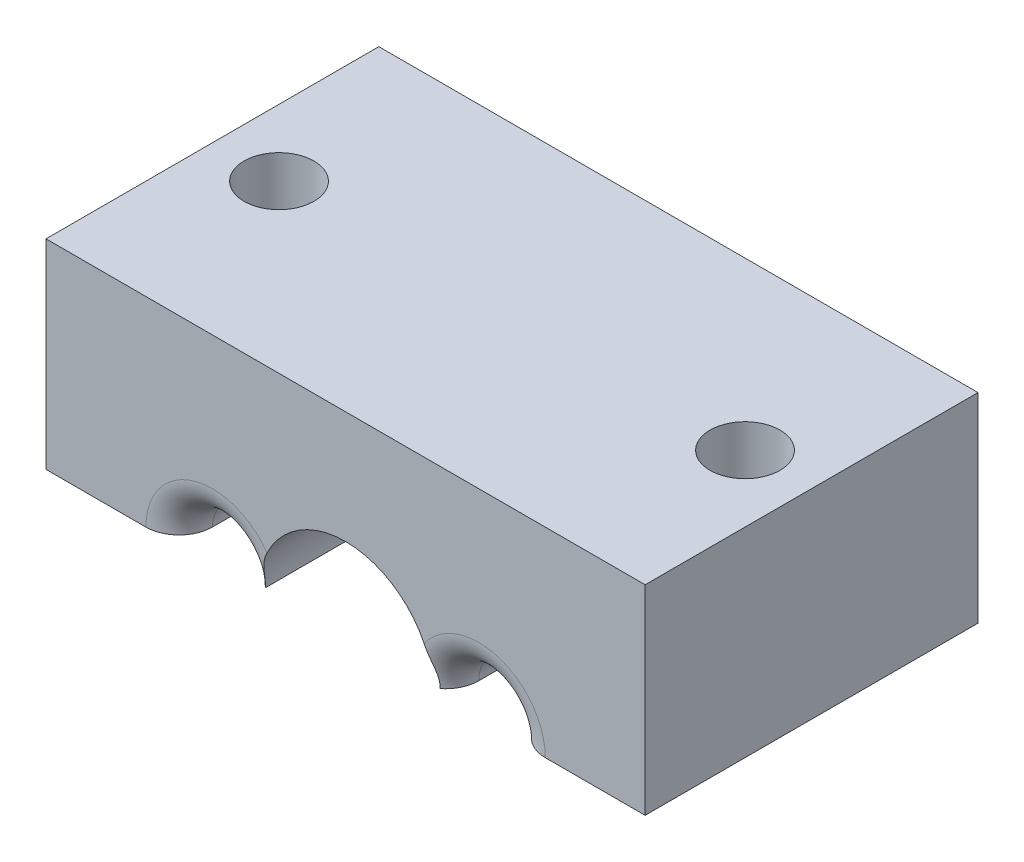
SolidWorks part; units mm, degrees
ref_plane "Front Plane" through (0, 0, 0) normal (0, 0, 1) x (1, 0, 0)
ref_plane "Top Plane" through (0, 0, 0) normal (0, 1, 0) x (1, 0, 0)
ref_plane "Right Plane" through (0, 0, 0) normal (1, 0, 0) x (0, 0, -1)
sketch "Sketch1" plane through (0, 0, 0) normal (0, 0, 1) x (1, 0, 0)
  line L0 (-20.9514, 2.8919) -> (8.9198, 2.8919)
  line L1 (28.9198, 2.8919) -> (43.9708, 2.8919)
  line L2 (0.9198, 2.8919) -> (0.9198, 14.8919)
  line L3 (0.9198, 14.8919) -> (36.9198, 14.8919)
  line L4 (36.9198, 2.8919) -> (36.9198, 14.8919)
  line L5 (12.9198, 2.8919) -> (13.6698, 2.8919)
  line L6 (24.1698, 2.8919) -> (24.9198, 2.8919)
  arc A0 (24.1698, 2.8919) -> (13.6698, 2.8919) centre (18.9198, 2.8919) ccw
  arc A1 (12.9198, 2.8919) -> (8.9198, 2.8919) centre (10.9198, 2.8919) ccw
  arc A2 (28.9198, 2.8919) -> (24.9198, 2.8919) centre (26.9198, 2.8919) ccw
  dimension "D5" = 10.5
  dimension "D8" = 4
  dimension "D1" = 12
  dimension "D2" = 12
  dimension "D3" = 18
  dimension "D4" = 36
  dimension "D6" = 8
  dimension "D7" = 16
extrude "Boss-Extrude1" add sketch "Sketch1" along normal blind 20 contours A2 L1 L4 L3 L2 L0 A1 L5 A0 L6
sketch "Sketch2" plane through (0, 2.8919, 0) normal (0, -1, 0) x (1, 0, 0)
  line L0 (13.6698, 20) -> (13.6698, 0) construction
  line L1 (13.6698, 13.8) -> (14.4698, 13.8)
  line L2 (13.6698, 13.8) -> (13.6698, 13)
  line L3 (13.6698, 13) -> (14.4698, 13)
  line L4 (14.4698, 13.8) -> (14.4698, 13)
  line L5 (13.6698, 10.8) -> (14.4698, 10.8)
  line L6 (13.6698, 10.8) -> (13.6698, 10)
  line L7 (13.6698, 10) -> (14.4698, 10)
  line L8 (14.4698, 10.8) -> (14.4698, 10)
  line L9 (13.6698, 7.8) -> (14.4698, 7.8)
  line L10 (13.6698, 7.8) -> (13.6698, 7)
  line L11 (13.6698, 7) -> (14.4698, 7)
  line L12 (14.4698, 7.8) -> (14.4698, 7)
  line L13 (13.6698, 4.8) -> (14.4698, 4.8)
  line L14 (13.6698, 4.8) -> (13.6698, 4)
  line L15 (13.6698, 4) -> (14.4698, 4)
  line L16 (14.4698, 4.8) -> (14.4698, 4)
  line L17 (13.6698, 0) -> (24.1698, 0) construction
  line L21 (13.6698, 20) -> (13.6698, 0) construction
  line L23 (13.6698, 1.8) -> (14.4698, 1.8) [skipped]
  line L24 (14.4698, 1.8) -> (14.4698, 1) [skipped]
  line L25 (13.6698, 1) -> (14.4698, 1) [skipped]
  line L26 (13.6698, 1.8) -> (13.6698, 1) [skipped]
  dimension "D1" = 0.8
  dimension "D2" = 0.8
  dimension "D4" = 4
  dimension "D5" = 3
  dimension "D3" = 5
sweep "Sweep2" add profiles "Sketch2" path edge at (18.9198, 8.1419, 20)
chamfer "Chamfer1" distance 0.4 angle 45 8 edges at (18.9198, 7.3419, 4) (18.9198, 7.3419, 4.8) (18.9198, 7.3419, 7) (18.9198, 7.3419, 7.8) (18.9198, 7.3419, 13.8) (18.9198, 7.3419, 13) (18.9198, 7.3419, 10.8) (18.9198, 7.3419, 10)
fillet "Fillet2" radius 2 4 edges at (10.9198, 4.8919, 0) (26.9198, 4.8919, 0) (26.9198, 4.8919, 20) (10.9198, 4.8919, 20)
sketch "Sketch3" plane through (0, 2.8919, 0) normal (0, -1, 0) x (1, 0, 0)
  line L0 (0.9198, 20) -> (0.9198, 0) construction
  line L1 (36.9198, 20) -> (36.9198, 0) construction
  line L2 (0.9198, 20) -> (6.9198, 20) construction
  circle A0 centre (32.9198, 10) radius 2.1
  circle A1 centre (4.9198, 10) radius 2.1
  dimension "D1" = 4.2
  dimension "D2" = 4.2
  dimension "D3" = 4
  dimension "D4" = 4
  dimension "D5" = 10
extrude "Cut-Extrude1" cut sketch "Sketch3" against normal through all
